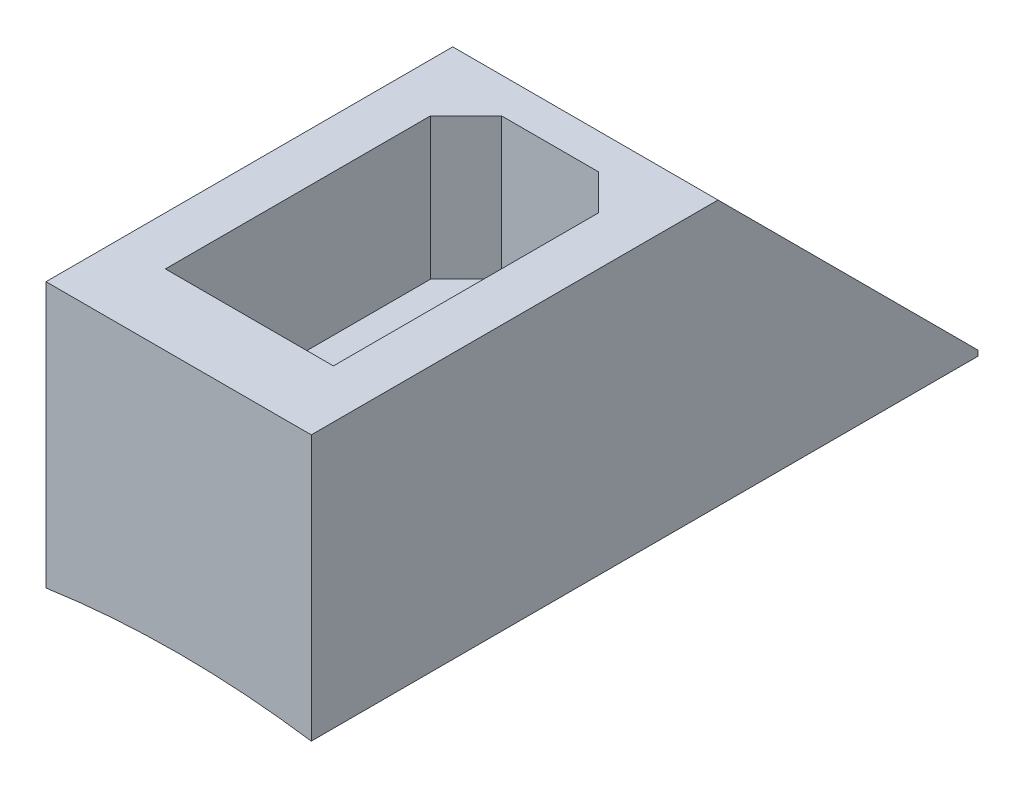
SolidWorks part; units mm, degrees
material "ABS"
ref_plane "Front Plane" through (0, 0, 0) normal (0, 0, 1) x (1, 0, 0)
ref_plane "Top Plane" through (0, 0, 0) normal (0, 1, 0) x (1, 0, 0)
ref_plane "Right Plane" through (0, 0, 0) normal (1, 0, 0) x (0, 0, -1)
sketch "Sketch1" plane through (0, 0, 0) normal (0, 0, 1) x (1, 0, 0)
  line L1 (0, 0) -> (15, 0)
  line L2 (0, 0) -> (0, 23.9388)
  line L3 (0, 23.9388) -> (15, 23.9388)
  line L4 (15, 0) -> (15, 23.9388)
  dimension "D1" = 15
extrude "Boss-Extrude1" add sketch "Sketch1" along normal blind 25
sketch "Sketch2" plane through (0, 0, 25) normal (0, 0, 1) x (1, 0, 0)
  line L0 (0, 23.9388) -> (0, 0) construction
  line L1 (15, 0) -> (15, 23.9388) construction
  line L2 (0, 8.9388) -> (15, 8.9388) construction
  line L3 (0, 8.9388) -> (0, 0)
  line L4 (0, 0) -> (15, 0)
  line L5 (15, 0) -> (15, 8.9388)
  line L6 (15, 23.9388) -> (0, 23.9388) construction
  arc A0 (0, 8.9388) -> (15, 8.9388) centre (7.5, -42.0748) cw
  dimension "D1" = 51.562
  dimension "D2" = 15
extrude "Cut-Extrude1" cut sketch "Sketch2" against normal blind 25
sketch "Sketch3" plane through (0, 23.9388, 0) normal (0, 1, 0) x (1, 0, 0)
  line L0 (7.5, 0) -> (7.5, -25) construction
  line L1 (15, 0) -> (0, 0) construction
  line L2 (15, -25) -> (0, -25) construction
  line L3 (7.5, -16.175) -> (7.5, -8.825) construction
  line L4 (7.5, -16.175) -> (-7.5625, -16.175) construction
  line L5 (-7.5625, -16.175) -> (-7.5625, -8.825) construction
  line L6 (-7.5625, -8.825) -> (7.5, -8.825) construction
  line L7 (-7.5625, -12.5) -> (7.5, -12.5) construction
  circle A0 centre (7.5, -8.825) radius 2.75
  circle A1 centre (7.5, -16.175) radius 2.75
  dimension "D2" = 5.5
  dimension "D1" = 3.675
extrude "Cut-Extrude2" cut sketch "Sketch3" against normal through all both and the other way through all
sketch "Sketch4" plane through (0, 23.9388, 0) normal (0, 1, 0) x (1, 0, 0)
  line L0 (2.75, -12.5) -> (0, -12.5) construction
  line L1 (2.75, -4) -> (12.25, -4)
  line L2 (2.75, -4) -> (2.75, -21)
  line L3 (2.75, -21) -> (12.25, -21)
  line L4 (12.25, -4) -> (12.25, -21)
  line L6 (7.5, -4) -> (7.5, 0) construction
  line L7 (15, 0) -> (0, 0) construction
  line L8 (0, -25) -> (0, 0) construction
  line L10 (7.5, -21) -> (7.5, -25) construction
  line L11 (15, -25) -> (0, -25) construction
  line L12 (12.25, -12.5) -> (15, -12.5) construction
  line L13 (15, -25) -> (15, 0) construction
  dimension "D1" = 9.5
  dimension "D2" = 17
extrude "Cut-Extrude3" cut sketch "Sketch4" against normal blind 8
chamfer "Chamfer1" distance 2 angle 45 2 edges at (12.25, 19.9388, 4) (2.75, 19.9388, 4)
sketch "Sketch5" plane through (0, 0, 0) normal (0, 0, -1) x (-1, 0, 0)
  line L0 (-15, 23.9388) -> (0, 23.9388)
  line L1 (0, 23.9388) -> (0, 8.9388)
  line L2 (-15, 8.9388) -> (-15, 23.9388)
  arc A0 (0, 8.9388) -> (-15, 8.9388) centre (-7.5, -42.0748) ccw
extrude "Boss-Extrude2" add sketch "Sketch5" along normal blind 12.7
chamfer "Chamfer2" distance 14.7 angle 45 1 edges at (7.5, 23.9388, -12.7)
